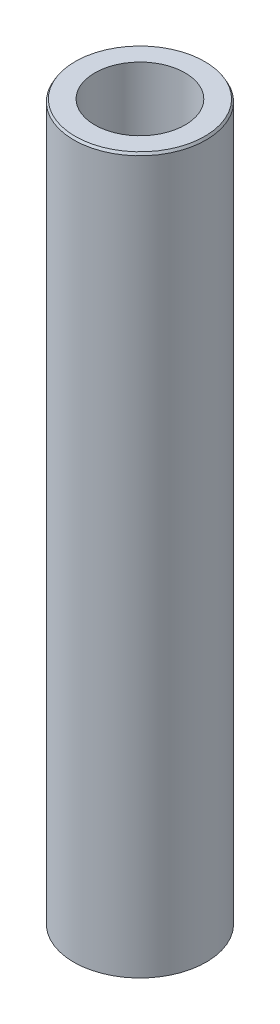
SolidWorks part; units mm, degrees
ref_plane "Front Plane" through (0, 0, 0) normal (0, 0, 1) x (1, 0, 0)
ref_plane "Top Plane" through (0, 0, 0) normal (0, 1, 0) x (1, 0, 0)
ref_plane "Right Plane" through (0, 0, 0) normal (1, 0, 0) x (0, 0, -1)
sketch "Sketch1" plane through (0, 0, 0) normal (0, 1, 0) x (1, 0, 0)
  circle A0 centre (0, 0) radius 10
  dimension "SHAFT_OD" = 20
extrude "Boss-Extrude1" add sketch "Sketch1" along normal blind 108.1123
sketch "Sketch2" plane through (0, 0, 0) normal (0, 1, 0) x (1, 0, 0)
  circle A0 centre (0, 0) radius 6.8219
  dimension "BORE_D" = 13.6438
extrude "Cut-Extrude1" cut sketch "Sketch2" along normal through all
chamfer "Chamfer1" distance 0.3705 angle 30 2 edges at (0, 108.1123, 10) (0, 0, 10) first distance on face at (0, 108.1123, 10) first distance on face at (0, 0, 6.8219)
